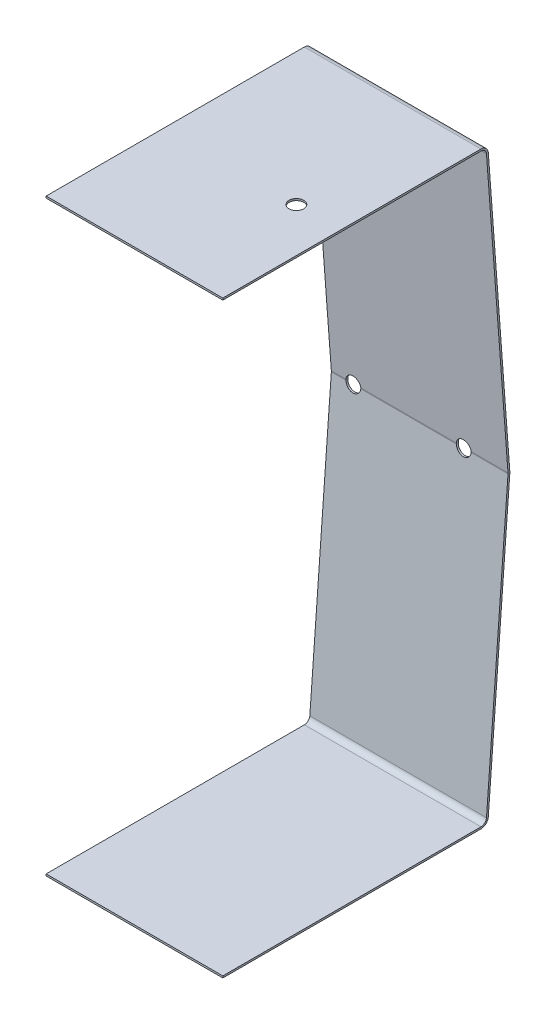
SolidWorks part; units mm, degrees
ref_plane "Front Plane" through (0, 0, 0) normal (0, 0, 1) x (1, 0, 0)
ref_plane "Top Plane" through (0, 0, 0) normal (0, 1, 0) x (1, 0, 0)
ref_plane "Right Plane" through (0, 0, 0) normal (1, 0, 0) x (0, 0, -1)
sketch "Sketch1" plane through (0, 0, 0) normal (0, 0, 1) x (1, 0, 0)
  line L0 (-76.2, 254) -> (-76.2, -254) construction
  line L1 (-76.2, 254) -> (76.2, 254)
  line L2 (-76.2, 254) -> (-76.2, -254)
  line L3 (-76.2, -254) -> (76.2, -254)
  line L4 (76.2, 254) -> (76.2, -254)
  line L5 (76.2, 254) -> (76.2, -254) construction
  line L6 (-76.2, 254) -> (76.2, -254) construction
  dimension "D1" = 508
extrude "Extrude1" add sketch "Sketch1" against normal offset from surface (228.6 mm away) 101.6
sketch "Sketch2" plane through (76.2, 0, 0) normal (1, 0, 0) x (0, 0, -1)
  line L0 (228.6, 254) -> (247.65, 0)
  line L1 (247.65, 0) -> (228.6, -254)
  line L2 (228.6, -254) -> (228.6, 254)
  line L3 (247.65, 0) -> (0, 0) construction
  dimension "D1" = 19.05
extrude "Extrude2" add sketch "Sketch2" against normal up to surface (152.4 mm away) up to face at (-76.2, 0, -114.3)
fillet "Fillet1" radius 6.35 3 edges at (0, 254, -228.6) (0, 0, -247.65) (0, -254, -228.6)
shell "Shell1" thickness 1.5875 removed face at (0, 0, 0) removed face at (76.2, 0, -175.1313) removed face at (-76.2, 0, -175.1313)
sketch "Sketch3" plane through (0, 0, 0) normal (0, 0, 1) x (1, 0, 0)
  line L0 (-76.2, 0.3562) -> (-76.2, 248.0062) construction
  line L1 (76.2, 0.3562) -> (76.2, 248.0062) construction
  circle A0 centre (-57.15, 0) radius 6.35
  circle A1 centre (38.1, 0) radius 6.35
  dimension "D3" = 12.7
  dimension "D1" = 19.05
  dimension "D2" = 38.1
extrude "Cut-Extrude1" cut sketch "Sketch3" against normal through all
sketch "Sketch4" plane through (0, 254, 0) normal (0, 1, 0) x (1, 0, 0)
  line L0 (76.2, 222.7084) -> (76.2, 0) construction
  line L1 (76.2, 0) -> (-76.2, 0) construction
  circle A0 centre (38.1, 101.6) radius 6.35
  dimension "D1" = 12.7
  dimension "D2" = 38.1
  dimension "D3" = 101.6
extrude "Cut-Extrude2" cut sketch "Sketch4" against normal up to next
